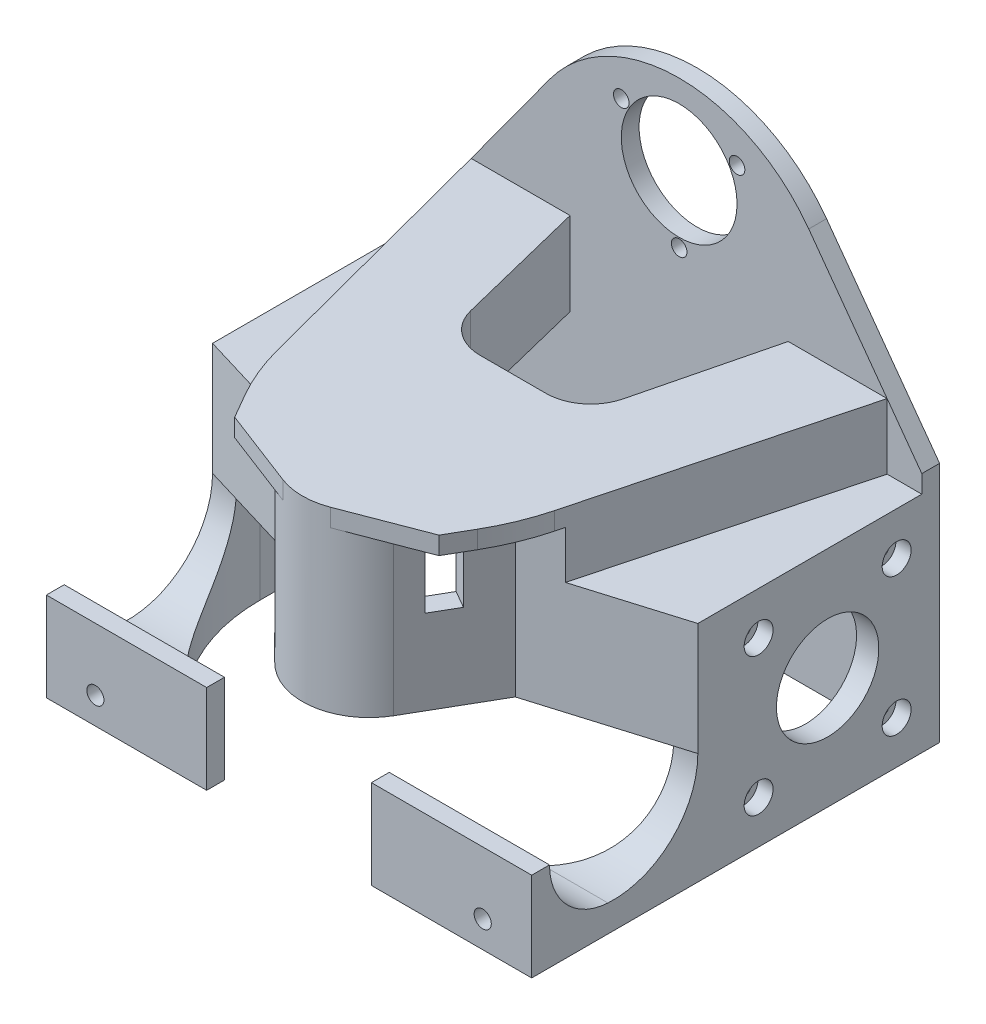
SolidWorks part; units mm, degrees
ref_plane "Plan de face" through (0, 0, 0) normal (0, 0, 1) x (1, 0, 0)
ref_plane "Plan de dessus" through (0, 0, 0) normal (0, 1, 0) x (1, 0, 0)
ref_plane "Plan de droite" through (0, 0, 0) normal (1, 0, 0) x (0, 0, -1)
sketch "Esquisse1" plane through (0, 0, 0) normal (0, 0, 1) x (1, 0, 0)
  line L1 (24.5, -21.15) -> (-24.5, -21.15)
  line L2 (24.5, -21.15) -> (24.5, 21.15)
  line L3 (24.5, 21.15) -> (-24.5, 21.15)
  line L4 (-24.5, -21.15) -> (-24.5, 21.15)
  line L5 (24.5, -21.15) -> (-24.5, 21.15) construction
  line L6 (24.5, 21.15) -> (-24.5, -21.15) construction
  line L7 (-24, 35.85) -> (24, 35.85)
  line L8 (-24, 35.85) -> (-24, -44.15)
  line L9 (-24, -44.15) -> (24, -44.15)
  line L10 (24, 35.85) -> (24, -44.15)
  line L11 (-25, 78.85) -> (25, 78.85)
  line L12 (-25, 78.85) -> (-25, -21.15)
  line L13 (-25, -21.15) -> (25, -21.15)
  line L14 (25, 78.85) -> (25, -21.15)
  point P0 (0, 0)
  point P10 (0, -44.15)
  point P11 (0, -21.15)
  dimension "D1" = 42.3
  dimension "D2" = 49
  dimension "D3" = 80
  dimension "D4" = 48
  dimension "D5" = 23
  dimension "D6" = 100
  dimension "D7" = 50
sketch "Esquisse2" plane through (0, 0, 0) normal (0, 0, 1) x (1, 0, 0)
  line L0 (-54.5, 29.15) -> (-29.1056, 64.0364)
  line L1 (-54.5, -25.15) -> (54.5, -25.15)
  line L2 (-54.5, -25.15) -> (-54.5, 29.15)
  line L4 (54.5, -25.15) -> (54.5, 29.15)
  line L5 (54.5, 29.15) -> (29.1056, 64.0364)
  line L7 (-24.5, -21.15) -> (-24.5, 21.15) construction
  line L8 (24.5, -21.15) -> (-24.5, -21.15) construction
  line L9 (0, -55) -> (0, 55) construction
  line L10 (-29.1056, 64.0364) -> (29.1056, 64.0364) construction
  line L11 (24.5, 21.15) -> (-24.5, 21.15) construction
  line L12 (-25, 78.85) -> (25, 78.85) construction
  arc A1 (-29.1056, 64.0364) -> (29.1056, 64.0364) centre (0, 42.85) cw
  point P4 (0, 64.0364)
  point P8 (0, -25.15)
  dimension "D1" = 5
  dimension "D3" = 8
  dimension "D4" = 36
  dimension "D2" = 4
extrude "Boss.-Extru.1" add sketch "Esquisse2" along normal blind 4
sketch "Esquisse3" plane through (-54.5, 0, 0) normal (-1, 0, 0) x (0, 0, 1)
  line L0 (4, -25.15) -> (4, 25.15)
  line L1 (4, -25.15) -> (46.3, -25.15)
  line L2 (4, 25.15) -> (46.3, 25.15)
  line L3 (46.3, -25.15) -> (46.3, 25.15)
  line L4 (4, -25.15) -> (46.3, 25.15) construction
  line L5 (46.3, -25.15) -> (4, 25.15) construction
  circle A0 centre (25.15, 0) radius 11.5
  point P6 (46.3, 0)
  dimension "D2" = 23
  dimension "D1" = 42.3
  dimension "D3" = 50.3
extrude "Boss.-Extru.2" add sketch "Esquisse3" against normal blind 5
hole_wizard "Chambrage pour vis à six pans creux M31" positions "Esquisse3D1" profile "Esquisse4" counterbore size "M3" standard "ISO" end condition through all
sketch3d "Esquisse3D1"
  line L0 (-54.5, 15.5, 9.65) -> (-54.5, -15.5, 40.65) construction
  line L2 (-54.5, 15.5, 40.65) -> (-54.5, -15.5, 9.65) construction
  line L3 (-54.5, 15.5, 40.65) -> (-54.5, -15.5, 40.65) construction
  line L4 (-54.5, -15.5, 40.65) -> (-54.5, -15.5, 9.65) construction
  line L6 (-54.5, -15.5, 9.65) -> (-54.5, 15.5, 9.65) construction
  line L7 (-54.5, 15.5, 9.65) -> (-54.5, 15.5, 40.65) construction
  line L9 (-54.5, 15.5, 40.65) -> (-54.5, 25.15, 40.65) construction
  line L10 (-54.5, 25.15, 46.3) -> (-54.5, 25.15, 4) construction
  line L15 (-54.5, -15.5, 40.65) -> (-54.5, -25.15, 40.65) construction
  line L16 (-54.5, -25.15, 46.3) -> (-54.5, -25.15, 0) construction
  line L18 (-54.5, 15.5, 40.65) -> (-54.5, 15.5, 46.3) construction
  line L19 (-54.5, -25.15, 46.3) -> (-54.5, 25.15, 46.3) construction
  line L21 (-54.5, 25.15, 4) -> (-54.5, -25.1646, 4) construction
  line L23 (-54.5, 15.5, 9.65) -> (-54.5, 15.5, 4) construction
  point P0 (-54.5, 15.5, 40.65)
  point P2 (-54.5, -15.5, 40.65)
  point P4 (-54.5, 15.5, 9.65)
  point P6 (-54.5, -15.5, 9.65)
  dimension "D1" = 31
sketch "Esquisse4" plane through (-54.5, 15.5, 40.65) normal (0, 1, 0) x (0, 0, 1)
  line L0 (0, 0) -> (0, 109)
  line L1 (0, 109) -> (1.7, 109)
  line L3 (1.7, 109) -> (1.7, 3.4)
  line L4 (1.7, 3.4) -> (3.25, 3.4)
  line L5 (3.25, 3.4) -> (3.25, 0)
  line L7 (3.25, 0) -> (0, 0)
  line L11 (0, -6.35) -> (0, 107.95) construction
  dimension "Diamètre du perçage jusqu'au prochain" = 3.4
  dimension "Profondeur du perçage jusqu'au prochain" = 109
  dimension "Diamètre du chambrage" = 6.5
  dimension "Profondeur du chambrage" = 3.4
sketch "Esquisse5" plane through (0, -25.15, 0) normal (0, -1, 0) x (1, 0, 0)
  line L0 (-49.5, 29) -> (-24.5, 4)
  line L1 (-49.5, 4) -> (-49.5, 46.3) construction
  line L2 (-49.5, 4) -> (54.5, 4) construction
  line L3 (-24.5, 4) -> (-49.5, 4)
  line L4 (-49.5, 4) -> (-49.5, 29)
  dimension "D1" = 25
extrude "Boss.-Extru.3" add sketch "Esquisse5" against normal blind 4
mirror "Symétrie1" about plane through (0, 0, 0) normal (0, 1, 0) of "Boss.-Extru.3"
mirror "Symétrie2" about plane through (0, 0, 0) normal (1, 0, 0) of "Symétrie1", "Boss.-Extru.3", "Chambrage pour vis à six pans creux M31", "Boss.-Extru.2"
sketch "Esquisse6" plane through (0, 25.15, 0) normal (0, 1, 0) x (1, 0, 0)
  line L0 (-49.5, -46.3) -> (49.5, -46.3)
  line L1 (-49.5, -46.3) -> (-49.5, -29)
  line L3 (-15, -42.3) -> (15, -42.3)
  line L5 (49.5, -29) -> (49.5, -46.3)
  line L6 (-49.5, -29) -> (-24.5, -4)
  line L7 (-24.5, -4) -> (-15, -42.3)
  line L8 (15, -42.3) -> (24.5, -4)
  line L9 (24.5, -4) -> (49.5, -29)
  point P10 (0, -42.3)
  dimension "D1" = 30
  dimension "D2" = 4
extrude "Boss.-Extru.4" add sketch "Esquisse6" against normal blind 4
ref_plane "Plan1" through (0, 35.85, 0) normal (0, 1, 0) x (1, 0, 0)
sketch "Esquisse7" plane through (0, 35.85, 0) normal (0, 1, 0) x (1, 0, 0)
  line L0 (-10, -46.3) -> (10, -46.3)
  line L1 (54.5, -46.3) -> (-54.5, -46.3) construction
  line L2 (0, -46.3) -> (0, -62.0735) construction
  line L3 (0, -62.0735) -> (-13.6603, -69.9603) construction
  line L4 (0, -62.0735) -> (13.6603, -69.9603) construction
  line L5 (-18.6603, -61.3) -> (-8.6603, -78.6205)
  line L6 (18.6603, -61.3) -> (8.6603, -78.6205)
  line L7 (-20, -59.2834) -> (-20, -50.3004) construction
  line L8 (20, -71.1495) -> (20, -58.0915) construction
  line L9 (-10, -41.3) -> (10, -41.3)
  line L10 (22.9904, -63.8) -> (12.9904, -81.1205)
  line L11 (-22.9904, -63.8) -> (-12.9904, -81.1205)
  line L12 (25, -71.1495) -> (25, -58.0915)
  arc A0 (-10, -46.3) -> (-18.6603, -61.3) centre (-10, -56.3) ccw
  arc A1 (10, -46.3) -> (18.6603, -61.3) centre (10, -56.3) cw
  arc A2 (-8.6603, -78.6205) -> (8.6603, -78.6205) centre (0, -73.6205) ccw
  arc A3 (10, -41.3) -> (22.9904, -63.8) centre (10, -56.3) cw
  arc A4 (-12.9904, -81.1205) -> (12.9904, -81.1205) centre (0, -73.6205) ccw
  arc A5 (-10, -41.3) -> (-22.9904, -63.8) centre (-10, -56.3) ccw
  point P4 (0, -46.3)
  dimension "D1" = 40
  dimension "D2" = 10
  dimension "D3" = 5
extrude "Boss.-Extru.5" add sketch "Esquisse7" against normal offset from surface (36 mm away) 25 up to face at (0, -25.15, 25.12)
sketch "Esquisse8" plane through (0, 0, 0) normal (1, 0, 0) x (0, 0, -1)
  line L1 (-46.3, 21.15) -> (-56.5339, 21.15) construction
  line L2 (-51.3, 16.15) -> (-51.3, -0.15)
  line L3 (-63.8, -0.15) -> (-41.3, -0.15) construction
  line L4 (-46.3, -25.15) -> (-46.3, 25.15) construction
  line L5 (-51.3, -0.15) -> (-41.3, -0.15)
  line L7 (-41.3, -0.15) -> (-41.3, 21.15)
  line L8 (-41.3, 21.15) -> (-46.3, 21.15)
  arc A0 (-46.3, 21.15) -> (-51.3, 16.15) centre (-46.3, 16.15) ccw
  dimension "D1" = 5
  dimension "D2" = 5
extrude "Enlèv. mat.-Extru.1" cut sketch "Esquisse8" against normal up to next and the other way up to next
sketch "Esquisse9" plane through (0, 35.85, 0) normal (0, 1, 0) x (1, 0, 0)
  line L0 (-10.2144, -75.9287) -> (-10.9144, -74.7163)
  line L1 (-10.2144, -75.9287) -> (-11.6, -76.7287)
  line L2 (-10.9144, -74.7163) -> (-12.3, -75.5163)
  line L3 (-11.6, -76.7287) -> (-12.3, -75.5163)
  line L4 (-18.6603, -61.3) -> (-8.6603, -78.6205) construction
  line L5 (10.2144, -75.9287) -> (10.9144, -74.7163)
  line L6 (10.2144, -75.9287) -> (11.6, -76.7287)
  line L7 (10.9144, -74.7163) -> (12.3, -75.5163)
  line L8 (11.6, -76.7287) -> (12.3, -75.5163)
  line L9 (8.6603, -78.6205) -> (18.6603, -61.3) construction
  dimension "D1" = 1.6
  dimension "D2" = 1.4
  dimension "D3" = 24.6
extrude "Enlèv. mat.-Extru.2" cut sketch "Esquisse9" against normal through all both
sketch "Esquisse11" plane through (0, -0.15, 0) normal (0, -1, 0) x (1, 0, 0)
  line L9 (-11.0644, 74.4565) -> (-12.7098, 75.4065)
  line L10 (-12.7098, 75.4065) -> (-11.7098, 77.1385)
  line L11 (-11.7098, 77.1385) -> (-10.0644, 76.1885)
  line L12 (-11.0644, 74.4565) -> (-12.7098, 75.4065)
  line L13 (-12.7098, 75.4065) -> (-11.7098, 77.1385)
  line L14 (-11.7098, 77.1385) -> (-10.0644, 76.1885)
  line L18 (-11.0644, 74.4565) -> (-10.0644, 76.1885)
  line L19 (10.0644, 76.1885) -> (11.0644, 74.4565)
  line L21 (12.7098, 75.4065) -> (11.0644, 74.4565)
  line L22 (11.7098, 77.1385) -> (12.7098, 75.4065)
  line L23 (10.0644, 76.1885) -> (11.7098, 77.1385)
  line L24 (12.7098, 75.4065) -> (11.0644, 74.4565)
  line L25 (11.7098, 77.1385) -> (12.7098, 75.4065)
  line L26 (10.0644, 76.1885) -> (11.7098, 77.1385)
  dimension "D1" = 0.3
  dimension "D2" = 0.3
extrude "Enlèv. mat.-Extru.3" cut sketch "Esquisse11" against normal through all both
sketch "Esquisse12" plane through (0, 35.85, 0) normal (0, 1, 0) x (1, 0, 0)
  line L0 (-11.25, -74.1349) -> (-14.4, -68.679)
  line L1 (-12.8954, -75.0849) -> (-15.5801, -76.6349)
  line L2 (-14.4, -68.679) -> (-18.7301, -71.179)
  line L3 (-15.5801, -76.6349) -> (-18.7301, -71.179)
  line L4 (-18.6603, -61.3) -> (-11.0644, -74.4565) construction
  line L5 (-22.9904, -63.8) -> (-12.9904, -81.1205) construction
  line L6 (11.25, -74.1349) -> (14.4, -68.679)
  line L7 (12.8954, -75.0849) -> (15.5801, -76.6349)
  line L8 (14.4, -68.679) -> (18.7301, -71.179)
  line L9 (15.5801, -76.6349) -> (18.7301, -71.179)
  line L10 (11.0644, -74.4565) -> (18.6603, -61.3) construction
  line L11 (12.9904, -81.1205) -> (22.9904, -63.8) construction
  line L12 (-11.0644, -74.4565) -> (-11.25, -74.1349)
  line L13 (-11.0644, -74.4565) -> (-12.7098, -75.4065)
  line L14 (-12.7098, -75.4065) -> (-12.8954, -75.0849)
  line L15 (11.25, -74.1349) -> (11.0644, -74.4565)
  line L16 (11.0644, -74.4565) -> (12.7098, -75.4065)
  line L17 (12.7098, -75.4065) -> (12.8954, -75.0849)
  dimension "D1" = 6.3
  dimension "D2" = 22.5
extrude "Enlèv. mat.-Extru.4" cut sketch "Esquisse12" against normal blind 17
sketch "Esquisse13" plane through (0, 35.85, 0) normal (0, 1, 0) x (1, 0, 0)
  line L0 (9.0933, -78.8705) -> (19.0933, -61.55)
  line L1 (10, -45.8) -> (-10, -45.8)
  line L2 (-19.0933, -61.55) -> (-9.0933, -78.8705)
  line L9 (8.6603, -78.6205) -> (18.6603, -61.3)
  line L10 (10, -46.3) -> (-10, -46.3)
  line L11 (-18.6603, -61.3) -> (-8.6603, -78.6205)
  line L12 (8.6603, -78.6205) -> (18.6603, -61.3)
  line L13 (10, -46.3) -> (-10, -46.3)
  line L14 (-18.6603, -61.3) -> (-8.6603, -78.6205)
  arc A0 (19.0933, -61.55) -> (10, -45.8) centre (10, -56.3) ccw
  arc A1 (-10, -45.8) -> (-19.0933, -61.55) centre (-10, -56.3) ccw
  arc A2 (-9.0933, -78.8705) -> (9.0933, -78.8705) centre (0, -73.6205) ccw
  arc A9 (-8.6603, -78.6205) -> (8.6603, -78.6205) centre (0, -73.6205) ccw
  arc A10 (18.6603, -61.3) -> (10, -46.3) centre (10, -56.3) ccw
  arc A11 (-10, -46.3) -> (-18.6603, -61.3) centre (-10, -56.3) ccw
  arc A12 (-8.6603, -78.6205) -> (8.6603, -78.6205) centre (0, -73.6205) ccw
  arc A13 (18.6603, -61.3) -> (10, -46.3) centre (10, -56.3) ccw
  arc A14 (-10, -46.3) -> (-18.6603, -61.3) centre (-10, -56.3) ccw
  dimension "D1" = 0.5
  dimension "D2" = 0
extrude "Enlèv. mat.-Extru.5" cut sketch "Esquisse13" against normal through all
sketch "Esquisse14" plane through (0, 35.85, 0) normal (0, 1, 0) x (1, 0, 0)
  line L0 (-15.5801, -76.6349) -> (-22.9413, -80.8849)
  line L1 (-22.9413, -80.8849) -> (-26.0913, -75.429)
  line L2 (-26.0913, -75.429) -> (-18.7301, -71.179)
  line L3 (10, -41.3) -> (-10, -41.3)
  line L4 (12.9904, -81.1205) -> (22.9904, -63.8)
  line L5 (-22.9904, -63.8) -> (-12.9904, -81.1205)
  line L6 (10, -41.3) -> (-10, -41.3)
  line L7 (12.9904, -81.1205) -> (15.5801, -76.6349)
  line L8 (-22.9904, -63.8) -> (-18.7301, -71.179)
  line L15 (-15.5801, -76.6349) -> (-12.9904, -81.1205)
  line L16 (15.5801, -76.6349) -> (22.9413, -80.8849)
  line L17 (22.9413, -80.8849) -> (26.0913, -75.429)
  line L18 (26.0913, -75.429) -> (18.7301, -71.179)
  line L19 (18.7301, -71.179) -> (22.9904, -63.8)
  line L20 (-23.4933, -73.929) -> (-20.3433, -79.3849) construction
  line L21 (20.3433, -79.3849) -> (23.4933, -73.929) construction
  line L22 (-14.833, -68.929) -> (-11.4974, -74.7065) construction
  line L23 (11.4974, -74.7065) -> (14.833, -68.929) construction
  arc A3 (22.9904, -63.8) -> (10, -41.3) centre (10, -56.3) ccw
  arc A4 (-12.9904, -81.1205) -> (12.9904, -81.1205) centre (0, -73.6205) ccw
  arc A5 (-10, -41.3) -> (-22.9904, -63.8) centre (-10, -56.3) ccw
  arc A6 (22.9904, -63.8) -> (10, -41.3) centre (10, -56.3) ccw
  arc A7 (-12.9904, -81.1205) -> (12.9904, -81.1205) centre (0, -73.6205) ccw
  arc A8 (-10, -41.3) -> (-22.9904, -63.8) centre (-10, -56.3) ccw
  dimension "D2" = 10
  dimension "D3" = 10
  dimension "D4" = 3
  dimension "D5" = 3
  dimension "D1" = 0
extrude "Boss.-Extru.6" add sketch "Esquisse14" along normal blind 4
sketch "Esquisse15" plane through (0, 25.15, 0) normal (0, 1, 0) x (1, 0, 0)
  line L0 (54.5, -46.3) -> (21.1803, -46.3) construction
  line L1 (-21.1803, -46.3) -> (-54.5, -46.3) construction
  line L2 (54.5, -46.3) -> (21.1803, -46.3)
  line L3 (-21.1803, -46.3) -> (-54.5, -46.3)
  line L6 (-54.5, -46.3) -> (-54.5, -54.3)
  line L7 (-54.5, -54.3) -> (-22.9904, -63.8)
  line L8 (54.5, -46.3) -> (54.5, -54.3)
  line L9 (54.5, -54.3) -> (22.9904, -63.8)
  arc A0 (22.9904, -63.8) -> (10, -41.3) centre (10, -56.3) ccw construction
  arc A1 (-10, -41.3) -> (-22.9904, -63.8) centre (-10, -56.3) ccw construction
  arc A2 (22.9904, -63.8) -> (21.1803, -46.3) centre (10, -56.3) ccw
  arc A3 (-21.1803, -46.3) -> (-22.9904, -63.8) centre (-10, -56.3) ccw
  dimension "D1" = 8
extrude "Boss.-Extru.7" add sketch "Esquisse15" against normal up to surface (25.3 mm away) up to face at (0, -0.15, 69.8151)
sketch "Esquisse16" plane through (0, -25.15, 0) normal (0, -1, 0) x (1, 0, 0)
  line L0 (-49.5, 29) -> (-49.5, 4)
  line L1 (-49.5, 46.3) -> (-49.5, 4) construction
  line L2 (-49.5, 4) -> (-24.5, 4)
  line L3 (-24.5, 4) -> (-49.5, 29)
  line L4 (24.5, 4) -> (49.5, 29)
  line L5 (49.5, 29) -> (49.5, 4)
  line L6 (49.5, 46.3) -> (49.5, 4) construction
  line L7 (49.5, 4) -> (24.5, 4) construction
  line L8 (49.5, 4) -> (24.5, 4)
extrude "Enlèv. mat.-Extru.6" cut sketch "Esquisse16" against normal blind 4
fillet "Congé2" radius 10 2 edges at (15.0324, 23.15, 42.1694) (-15.0324, 23.15, 42.1694)
sketch "Esquisse17" plane through (0, 35.85, 0) normal (0, -1, 0) x (1, 0, 0)
  line L0 (-23.4933, 73.929) -> (-21.9183, 76.657) construction
  line L1 (-18.7301, 71.179) -> (-26.0913, 75.429) construction
  line L2 (-21.9183, 76.657) -> (-20.3433, 79.3849) construction
  line L3 (-22.9413, 80.8849) -> (-15.5801, 76.6349) construction
  line L4 (-26.0913, 75.429) -> (-22.9413, 80.8849) construction
  line L5 (0, -55) -> (0, 55) construction
  line L6 (21.9183, 76.657) -> (20.3433, 79.3849) construction
  line L7 (23.4933, 73.929) -> (21.9183, 76.657) construction
  circle A0 centre (-21.9183, 76.657) radius 1.925
  circle A2 centre (21.9183, 76.657) radius 1.925
  dimension "D1" = 3.85
  dimension "D3" = 3
extrude "Enlèv. mat.-Extru.7" cut sketch "Esquisse17" against normal blind 3
sketch "Esquisse18" plane through (0, 39.85, 0) normal (0, 1, 0) x (1, 0, 0)
  line L0 (-31.1436, -63.1542) -> (-46.7113, -4)
  line L1 (-22.9413, -80.8849) -> (-26.0913, -75.429)
  line L2 (-17.1313, -33.7075) -> (-24.5, -4) construction
  line L3 (-26.0913, -75.429) -> (-22.9413, -80.8849) construction
  line L4 (-17.1313, -33.7075) -> (-24.5, -4)
  line L5 (-46.7113, -4) -> (-24.5, -4)
  line L6 (-22.9904, -63.8) -> (-12.9904, -81.1205)
  line L7 (-10, -41.3) -> (-7.4254, -41.3)
  line L8 (0, -55) -> (0, 55) construction
  line L9 (10, -41.3) -> (7.4254, -41.3)
  line L10 (22.9904, -63.8) -> (12.9904, -81.1205)
  line L11 (22.9413, -80.8849) -> (26.0913, -75.429)
  line L12 (31.1436, -63.1542) -> (46.7113, -4)
  line L13 (46.7113, -4) -> (24.5, -4)
  line L14 (17.1313, -33.7075) -> (24.5, -4)
  line L15 (-22.9413, -80.8849) -> (-5.373, -87.6252)
  line L16 (22.9413, -80.8849) -> (5.373, -87.6252)
  arc A0 (-26.0913, -75.429) -> (-31.1436, -63.1542) centre (17.2099, -50.429) cw
  arc A3 (-17.1313, -33.7075) -> (-7.4254, -41.3) centre (-7.4254, -31.3) ccw construction
  arc A4 (-17.1313, -33.7075) -> (-7.4254, -41.3) centre (-7.4254, -31.3) ccw
  arc A5 (-12.9904, -81.1205) -> (12.9904, -81.1205) centre (0, -73.6205) ccw construction
  arc A6 (-10, -41.3) -> (-22.9904, -63.8) centre (-10, -56.3) ccw construction
  arc A7 (-12.9904, -81.1205) -> (12.9904, -81.1205) centre (0, -73.6205) ccw
  arc A8 (-10, -41.3) -> (-22.9904, -63.8) centre (-10, -56.3) ccw
  arc A9 (10, -41.3) -> (22.9904, -63.8) centre (10, -56.3) cw
  arc A10 (26.0913, -75.429) -> (31.1436, -63.1542) centre (-17.2099, -50.429) ccw
  arc A11 (17.1313, -33.7075) -> (7.4254, -41.3) centre (7.4254, -31.3) cw
  arc M21 (-10, -41.3) -> (-22.9904, -63.8) centre (-10, -56.3) ccw
  line M22 (-22.9904, -63.8) -> (-18.7301, -71.179)
  line M23 (-18.7301, -71.179) -> (-26.0913, -75.429)
  line M25 (-22.9413, -80.8849) -> (-15.5801, -76.6349)
  line M26 (-15.5801, -76.6349) -> (-12.9904, -81.1205)
  arc M27 (-12.9904, -81.1205) -> (12.9904, -81.1205) centre (0, -73.6205) ccw
  line M28 (12.9904, -81.1205) -> (15.5801, -76.6349)
  line M29 (15.5801, -76.6349) -> (22.9413, -80.8849)
  line M31 (26.0913, -75.429) -> (18.7301, -71.179)
  line M32 (18.7301, -71.179) -> (22.9904, -63.8)
  arc M33 (22.9904, -63.8) -> (10, -41.3) centre (10, -56.3) ccw
  line M34 (10, -41.3) -> (-10, -41.3)
  dimension "D1" = 50
extrude "Boss.-Extru.8" add sketch "Esquisse18" against normal blind 4 contours A4 L4 L5 L0 A0 M23 M22 M21 M34 | M25 M29 M28 M27 M26 | L14 A11 A10 L12 L13 M34 M33 M32 M31 | L16 M29 M28 M27 region at (-29.6426, 39.85, 32.1523) region at (-15.8673, 39.85, 81.3467) region at (15.8673, 39.85, 81.3467) region at (29.6426, 39.85, 32.1523)
sketch "Esquisse20" plane through (0, 0, 0) normal (1, 0, 0) x (0, 0, -1)
  line L0 (-46.3, -0.15) -> (-46.3, 21.15) construction
  line L1 (-51.3, 16.15) -> (-51.3, -0.15) construction
  line L2 (-46.3, -0.15) -> (-46.3, 21.15)
  line L3 (-51.3, 16.15) -> (-51.3, -0.15)
  line L4 (-51.3, -0.15) -> (-46.3, -0.15)
  arc A0 (-46.3, 21.15) -> (-51.3, 16.15) centre (-46.3, 16.15) ccw construction
  arc A1 (-46.3, 21.15) -> (-51.3, 16.15) centre (-46.3, 16.15) ccw
extrude "Enlèv. mat.-Extru.8" cut sketch "Esquisse20" against normal up to surface (49.5 mm away) and the other way up to surface (49.5 mm away) up to face at (-49.5, -1.63, 29.38) other way up to face at (49.5, -1.63, 29.38)
sketch "Esquisse21" plane through (0, 39.85, 0) normal (0, 1, 0) x (1, 0, 0)
  line L0 (22.9904, -63.8) -> (54.5, -54.3) construction
  line L2 (54.5, -4) -> (24.5, -4) construction
  line L3 (24.5, -4) -> (17.1313, -33.7075) construction
  line L4 (7.4254, -41.3) -> (10, -41.3) construction
  line L5 (-10, -41.3) -> (-7.4254, -41.3) construction
  line L6 (-17.1313, -33.7075) -> (-24.5, -4) construction
  line L7 (-24.5, -4) -> (-54.5, -4) construction
  line L9 (-54.5, -54.3) -> (-22.9904, -63.8) construction
  line L10 (22.9904, -63.8) -> (31.6617, -61.1856)
  line L11 (22.9413, -80.8849) -> (26.0913, -75.429)
  line L12 (31.1436, -63.1542) -> (46.7113, -4)
  line L13 (46.7113, -4) -> (24.5, -4)
  line L14 (24.5, -4) -> (17.1313, -33.7075)
  line L15 (7.4254, -41.3) -> (-7.4254, -41.3)
  line L16 (-17.1313, -33.7075) -> (-24.5, -4)
  line L17 (-24.5, -4) -> (-46.7113, -4)
  line L18 (-46.7113, -4) -> (-31.1436, -63.1542)
  line L19 (-26.0913, -75.429) -> (-22.9413, -80.8849)
  line L20 (-22.9413, -80.8849) -> (-5.373, -87.6252)
  line L21 (5.373, -87.6252) -> (22.9413, -80.8849)
  line L23 (31.6617, -61.1856) -> (46.7113, -4)
  line L24 (46.7113, -4) -> (24.5, -4)
  line L25 (24.5, -4) -> (17.1313, -33.7075)
  line L27 (-17.1313, -33.7075) -> (-24.5, -4)
  line L28 (-24.5, -4) -> (-46.7113, -4)
  line L29 (-46.7113, -4) -> (-31.6617, -61.1856)
  line L34 (46.7113, -4) -> (24.5, -4)
  line L35 (24.5, -4) -> (17.1313, -33.7075)
  line L36 (7.4254, -41.3) -> (10, -41.3)
  line L37 (-10, -41.3) -> (-7.4254, -41.3)
  line L38 (-17.1313, -33.7075) -> (-24.5, -4)
  line L39 (-24.5, -4) -> (-46.7113, -4)
  line L41 (-31.6617, -61.1856) -> (-22.9904, -63.8)
  arc A0 (22.9904, -63.8) -> (10, -41.3) centre (10, -56.3) ccw construction
  arc A1 (7.4254, -41.3) -> (17.1313, -33.7075) centre (7.4254, -31.3) ccw construction
  arc A2 (-10, -41.3) -> (-22.9904, -63.8) centre (-10, -56.3) ccw construction
  arc A3 (-17.1313, -33.7075) -> (-7.4254, -41.3) centre (-7.4254, -31.3) ccw construction
  arc A4 (22.9904, -63.8) -> (10, -41.3) centre (10, -56.3) ccw
  arc A5 (26.0913, -75.429) -> (31.1436, -63.1542) centre (-17.2099, -50.429) ccw
  arc A6 (7.4254, -41.3) -> (17.1313, -33.7075) centre (7.4254, -31.3) ccw
  arc A7 (-17.1313, -33.7075) -> (-7.4254, -41.3) centre (-7.4254, -31.3) ccw
  arc A8 (-31.1436, -63.1542) -> (-26.0913, -75.429) centre (17.2099, -50.429) ccw
  arc A9 (-5.373, -87.6252) -> (5.373, -87.6252) centre (0, -73.6205) ccw
  arc A11 (7.4254, -41.3) -> (17.1313, -33.7075) centre (7.4254, -31.3) ccw
  arc A12 (-17.1313, -33.7075) -> (-7.4254, -41.3) centre (-7.4254, -31.3) ccw
  arc A15 (7.4254, -41.3) -> (17.1313, -33.7075) centre (7.4254, -31.3) ccw
  arc A16 (-10, -41.3) -> (-22.9904, -63.8) centre (-10, -56.3) ccw
  arc A17 (-17.1313, -33.7075) -> (-7.4254, -41.3) centre (-7.4254, -31.3) ccw
  line M31 (31.1436, -63.1542) -> (46.7113, -4)
  line M32 (46.7113, -4) -> (24.5, -4)
  line M33 (24.5, -4) -> (17.1313, -33.7075)
  arc M34 (17.1313, -33.7075) -> (7.4254, -41.3) centre (7.4254, -31.3) cw
  arc M36 (-7.4254, -41.3) -> (-17.1313, -33.7075) centre (-7.4254, -31.3) cw
  line M37 (-17.1313, -33.7075) -> (-24.5, -4)
  line M38 (-24.5, -4) -> (-46.7113, -4)
  line M39 (-46.7113, -4) -> (-31.1436, -63.1542)
  dimension "D1" = 0
extrude "Boss.-Extru.11" add sketch "Esquisse21" against normal up to surface (14.7 mm away) contours A4 L10 L36 M31 M32 M33 M34 | A16 L37 L41 M36 M37 M38 M39 region at (30.0216, 39.85, 28.9195) region at (-30.0216, 39.85, 28.9195) up to face at (28.4073, 25.15, 34.3329)
sketch "Esquisse22" plane through (-54.5, 0, 0) normal (-1, 0, 0) x (0, 0, 1)
  line L0 (54.3, -0.15) -> (46.3, -0.15)
  line L1 (46.3, -0.15) -> (46.3, -25.15)
  line L2 (46.3, -25.15) -> (91.6205, -25.15)
  line L3 (91.6205, -25.15) -> (91.6205, -5.15)
  line L4 (91.6205, -5.15) -> (87.6205, -5.15)
  line L5 (54.3, -0.15) -> (54.3, 25.15) construction
  line L6 (67.409, -19.15) -> (70.4541, -19.15) construction
  line L7 (88.6205, -0.15) -> (88.6205, 39.85) construction
  arc A0 (87.6205, -5.15) -> (74.4892, -19.123) centre (73.6205, -5.15) cw
  arc A1 (74.4892, -19.123) -> (54.3, -0.15) centre (73.3097, -0.15) cw
  dimension "D3" = 6
  dimension "D1" = 20
  dimension "D2" = 4
  dimension "D4" = 3
extrude "Boss.-Extru.12" add sketch "Esquisse22" against normal blind 5
mirror "Symétrie3" about plane through (0, 0, 0) normal (1, 0, 0) of "Boss.-Extru.12"
sketch "Esquisse24" plane through (0, 0, 91.6205) normal (0, 0, 1) x (1, 0, 0)
  line L0 (-49.5, -5.15) -> (-18.5, -5.15)
  line L1 (-49.5, -5.15) -> (-49.5, -25.15)
  line L2 (-18.5, -5.15) -> (-18.5, -25.15)
  line L3 (-49.5, -25.15) -> (-18.5, -25.15)
  line L4 (-49.5, -25.15) -> (49.5, -25.15) construction
  line L5 (0, -25.15) -> (-43.5, -25.15) construction
  dimension "D1" = 43.5
  dimension "D2" = 25
extrude "Boss.-Extru.13" add sketch "Esquisse24" against normal blind 4
mirror "Symétrie7" about plane through (0, 0, 0) normal (1, 0, 0) of "Boss.-Extru.13"
fillet "Congé4" radius 40 2 edges at (-49.5, -15.15, 87.6205) (49.5, -15.15, 87.6205)
sketch "Esquisse25" plane through (0, 0, 91.6205) normal (0, 0, 1) x (1, 0, 0)
  line L0 (-18.5, -25.15) -> (-54.5, -25.15) construction
  circle A0 centre (-43.5, -19.15) radius 1.925
  dimension "D1" = 3.85
  dimension "D2" = 6
  dimension "D3" = 43.5
extrude "Enlèv. mat.-Extru.9" cut sketch "Esquisse25" against normal blind 4
mirror "Symétrie8" about plane through (0, 0, 0) normal (1, 0, 0) of "Enlèv. mat.-Extru.9"
sketch "Esquisse26" plane through (0, 0, 4) normal (0, 0, 1) x (1, 0, 0)
  line L0 (-13, 68.3556) -> (13, 68.3556) construction
  line L1 (13, 68.3556) -> (0, 45.8389) construction
  line L2 (0, 45.8389) -> (-13, 68.3556) construction
  circle A0 centre (0, 60.85) radius 13
  circle A1 centre (0, 45.8389) radius 1.75
  circle A2 centre (-13, 68.3556) radius 1.75
  circle A3 centre (13, 68.3556) radius 1.75
  circle A4 centre (0, 60.85) radius 15.0111 construction
  arc A5 (29.1056, 64.0364) -> (-29.1056, 64.0364) centre (0, 42.85) ccw construction
  point P15 (0, 78.85)
  dimension "D1" = 26
  dimension "D2" = 3.5
  dimension "D3" = 3.5
  dimension "D4" = 3.5
  dimension "D5" = 26
  dimension "D6" = 18
extrude "Enlèv. mat.-Extru.10" cut sketch "Esquisse26" against normal through all
